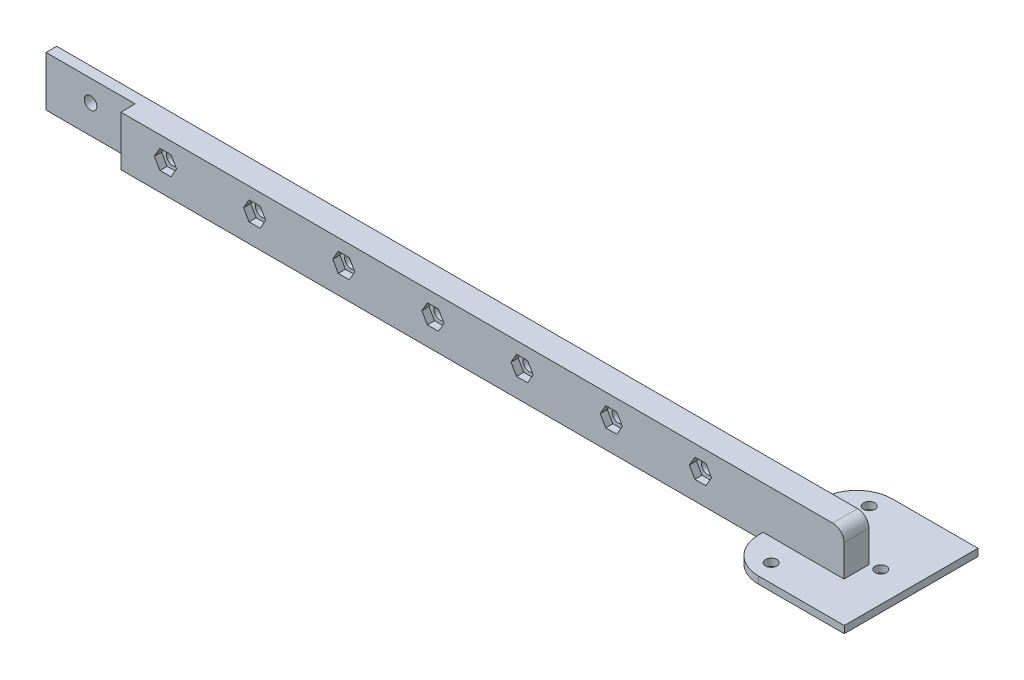
SolidWorks part; units mm, degrees
ref_plane "Front Plane" through (0, 0, 0) normal (0, 0, 1) x (1, 0, 0)
ref_plane "Top Plane" through (0, 0, 0) normal (0, 1, 0) x (1, 0, 0)
ref_plane "Right Plane" through (0, 0, 0) normal (1, 0, 0) x (0, 0, -1)
sketch "TopSketch1" plane through (0, 0, 0) normal (0, 1, 0) x (1, 0, 0)
  line L0 (0, 0) -> (34, 0)
  line L1 (34, 0) -> (34, 37.5)
  line L2 (34, 37.5) -> (0, 37.5)
  line L3 (0, 37.5) -> (0, 19.25)
  line L7 (0, 11.25) -> (0, 0)
  line L8 (0, 11.25) -> (-205.08, 11.25)
  line L9 (-205.08, 11.25) -> (-205.08, 19.25)
  line L10 (-205.08, 19.25) -> (0, 19.25)
  circle A0 centre (8.5, 32.5) radius 1.59
  circle A1 centre (8.5, 5) radius 1.59
  circle A3 centre (25.5, 18.75) radius 1.59
  dimension "D6" = 3.18
  dimension "D1" = 37.5
  dimension "D2" = 34
  dimension "D5" = 8.5
  dimension "D7" = 5
  dimension "D8" = 5
  dimension "D3" = 205.08
  dimension "D4" = 8
  dimension "D9" = 8.5
  dimension "D10" = 18.75
  dimension "D11" = 11.25
  dimension "D12" = 18.25
  dimension "D13" = 239.08
extrude "TopBoss-Extrude1" add sketch "TopSketch1" along normal blind 2
fillet "Fillet1" radius 10 2 edges at (0, 1, 0) (0, 1, -37.5)
sketch "LinearRailHEightSketch2" plane through (0, 2, 0) normal (0, 1, 0) x (1, 0, 0)
  line L1 (-205.08, 18.25) -> (22.6667, 18.25)
  line L2 (-205.08, 18.25) -> (-205.08, 11.25)
  line L3 (-205.08, 11.25) -> (22.6667, 11.25)
  line L4 (22.6667, 18.25) -> (22.6667, 11.25)
  line L5 (-205.08, 19.25) -> (-205.08, 11.25) construction
  line L6 (-205.08, 11.25) -> (0, 11.25) construction
  line L8 (34, 0) -> (34, 37.5) construction
  line L9 (0, 19.25) -> (-205.08, 19.25) construction
  dimension "D2" = 11.3333
  dimension "D1" = 1
extrude "LinearRailHeightBoss-Extrude2" add sketch "LinearRailHEightSketch2" along normal blind 12
sketch "LinearRailHolesSketch3" plane through (0, 0, -11.25) normal (0, 0, 1) x (1, 0, 0)
  line L0 (0, 2) -> (22.6667, 2) construction
  line L1 (-205.08, 14) -> (-205.08, 0) construction
  circle A0 centre (-192.58, 8) radius 1.75
  circle A1 centre (-167.58, 8) radius 1.75
  circle A2 centre (-142.58, 8) radius 1.75
  circle A3 centre (-117.58, 8) radius 1.75
  circle A4 centre (-92.58, 8) radius 1.75
  circle A5 centre (-67.58, 8) radius 1.75
  circle A6 centre (-42.58, 8) radius 1.75
  circle A7 centre (-17.58, 8) radius 1.75
  dimension "D4" = 8
  dimension "D1" = 3.5
  dimension "D2" = 6
  dimension "D3" = 12.5
extrude "LinearRailHolesCut-Extrude1" cut sketch "LinearRailHolesSketch3" against normal through all
sketch "ConnectingPlateSketch1" plane through (0, 0, -11.25) normal (0, 0, 1) x (1, 0, 0)
  line L0 (-205.08, 0) -> (0, 0) construction
  line L1 (-205.08, 14) -> (-180.08, 14)
  line L2 (-205.08, 14) -> (-205.08, 0)
  line L3 (-205.08, 0) -> (-180.08, 0)
  line L4 (-180.08, 14) -> (-180.08, 0)
  line L5 (-205.08, 14) -> (22.6667, 14) construction
  line L6 (-205.08, 14) -> (-205.08, 0) construction
  dimension "D1" = 25
extrude "ConnectingPlateCut-Extrude1" cut sketch "ConnectingPlateSketch1" against normal blind 4
fillet "Fillet2" radius 3.175 1 edges at (22.6667, 14, -14.75)
sketch "NutHoleSketch1" plane through (0, 0, -11.25) normal (0, 0, 1) x (1, 0, 0)
  line L1 (-166.03, 5.3153) -> (-164.48, 8)
  line L2 (-164.48, 8) -> (-166.03, 10.6847)
  line L3 (-166.03, 10.6847) -> (-169.13, 10.6847)
  line L4 (-169.13, 10.6847) -> (-170.68, 8)
  line L5 (-170.68, 8) -> (-169.13, 5.3153)
  line L6 (-169.13, 5.3153) -> (-166.03, 5.3153)
  line L7 (-141.03, 5.3153) -> (-139.48, 8)
  line L8 (-139.48, 8) -> (-141.03, 10.6847)
  line L9 (-141.03, 10.6847) -> (-144.13, 10.6847)
  line L10 (-144.13, 10.6847) -> (-145.68, 8)
  line L11 (-145.68, 8) -> (-144.13, 5.3153)
  line L12 (-144.13, 5.3153) -> (-141.03, 5.3153)
  line L13 (-116.03, 5.3153) -> (-114.48, 8)
  line L14 (-114.48, 8) -> (-116.03, 10.6847)
  line L15 (-116.03, 10.6847) -> (-119.13, 10.6847)
  line L16 (-119.13, 10.6847) -> (-120.68, 8)
  line L17 (-120.68, 8) -> (-119.13, 5.3153)
  line L18 (-119.13, 5.3153) -> (-116.03, 5.3153)
  line L19 (-91.03, 5.3153) -> (-89.48, 8)
  line L20 (-89.48, 8) -> (-91.03, 10.6847)
  line L21 (-91.03, 10.6847) -> (-94.13, 10.6847)
  line L22 (-94.13, 10.6847) -> (-95.68, 8)
  line L23 (-95.68, 8) -> (-94.13, 5.3153)
  line L24 (-94.13, 5.3153) -> (-91.03, 5.3153)
  line L25 (-66.03, 5.3153) -> (-64.48, 8)
  line L26 (-64.48, 8) -> (-66.03, 10.6847)
  line L27 (-66.03, 10.6847) -> (-69.13, 10.6847)
  line L28 (-69.13, 10.6847) -> (-70.68, 8)
  line L29 (-70.68, 8) -> (-69.13, 5.3153)
  line L30 (-69.13, 5.3153) -> (-66.03, 5.3153)
  line L31 (-41.03, 5.3153) -> (-39.48, 8)
  line L32 (-39.48, 8) -> (-41.03, 10.6847)
  line L33 (-41.03, 10.6847) -> (-44.13, 10.6847)
  line L34 (-44.13, 10.6847) -> (-45.68, 8)
  line L35 (-45.68, 8) -> (-44.13, 5.3153)
  line L36 (-44.13, 5.3153) -> (-41.03, 5.3153)
  line L37 (-16.03, 5.3153) -> (-14.48, 8)
  line L38 (-14.48, 8) -> (-16.03, 10.6847)
  line L39 (-16.03, 10.6847) -> (-19.13, 10.6847)
  line L40 (-19.13, 10.6847) -> (-20.68, 8)
  line L41 (-20.68, 8) -> (-19.13, 5.3153)
  line L42 (-19.13, 5.3153) -> (-16.03, 5.3153)
  circle A0 centre (-167.58, 8) radius 2.6847 construction
  circle A1 centre (-142.58, 8) radius 2.6847 construction
  circle A2 centre (-117.58, 8) radius 2.6847 construction
  circle A3 centre (-92.58, 8) radius 2.6847 construction
  circle A4 centre (-67.58, 8) radius 2.6847 construction
  circle A5 centre (-42.58, 8) radius 2.6847 construction
  circle A6 centre (-17.58, 8) radius 2.6847 construction
  dimension "D1" = 6.2
extrude "NutHoleSketcjCut-Extrude1" cut sketch "NutHoleSketch1" against normal blind 2
equation "\"GABDepth\"= \"GABDistanceFromBackToFirstPulley\" + \"GABPulleyDDistanceBetween\" + \"GABDistanceFromPulleyToFront\""
equation "\"GABWidth\"= \"StandardWallThickness\" + \"GABDistanceFromLSideToPulley\" + \"GABPulleyWDistanceBetween\" + \"GABDistanceFromPulleyToRSide\""
equation "\"StandardWallThickness\"= 3mm"
equation "\"LinearRailWidth\"= 12mm'Spec"
equation "\"LinearRailHeight\"= 8mm'Spec"
equation "\"GABLRClampHoleOffsetFromSide\"= 5mm"
equation "\"GABDistanceFromBackToFirstPulley\"= 13.5mm"
equation "\"GABPulleyDDistanceBetween\"= 12.5mm'From the100"
equation "\"GABPulleyWDistanceBetween\"= 14.5mm'From the100"
equation "\"GABDistanceFromPulleyToFront\"= 8mm"
equation "\"GABDistanceFromLSideToPulley\"= 9.5mm + \"StandardWallThickness\""
equation "\"GABDistanceFromPulleyToRSide\"= 7.5mm"
equation "\"GABClampBaseHeight\"= 2mm"
equation "\"LinearRailHoleDiameter\"= 3.5mm'Spec"
equation "\"GABDistanceToFrontRearClampHoles\"= 8.5mm"
equation "\"D1@TopSketch1\" = \"GABWidth\""
equation "\"D2@TopSketch1\"=\"GABDepth\""
equation "\"D5@TopSketch1\" = \"GABDistanceToFrontRearClampHoles\""
equation "\"D7@TopSketch1\" = \"GABLRClampHoleOffsetFromSide\""
equation "\"D8@TopSketch1\" = \"GABLRClampHoleOffsetFromSide\""
equation "\"D1@TopBoss-Extrude1\" = \"GABClampBaseHeight\""
equation "\"RailThickness\"= .125in'Spec"
equation "\"D4@TopSketch1\"=\"LinearRailHeight\""
equation "\"D1@LinearRailHeightBoss-Extrude2\" = \"LinearRailWidth\""
equation "\"D1@LinearRailHolesSketch3\" = \"LinearRailHoleDiameter\""
equation "\"D2@LinearRailHolesSketch3\" = \"LinearRailWidth\" / 2"
equation "\"D9@TopSketch1\"=\"GABDistanceToFrontRearClampHoles\""
equation "\"D2@LinearRailHEightSketch2\"=\"GABDepth\"/3"
equation "\"LinearRailHoleDistance\"= 25mm'Spec"
equation "\"D11@TopSketch1\"=\"GABWidth\"/2 -\"LinearRailHeight\" + 1/2"
equation "\"D1@ConnectingPlateSketch1\" = \"LinearRailHoleDistance\""
equation "\"D1@ConnectingPlateCut-Extrude1\" = \"LinearRailHeight\" / 2"
equation "\"D1@Fillet2\"=\"RailThickness\""
equation "\"LinearRailSupportNutWidth\"= 6.2mm"
equation "\"D1@NutHoleSketch1\" = \"LinearRailSupportNutWidth\""
equation "\"LinearRailSupportNutHoleDepth\" = \"LinearRailHeight\" / 4"
equation "\"D1@NutHoleSketcjCut-Extrude1\"=\"LinearRailSupportNutHoleDepth\""
